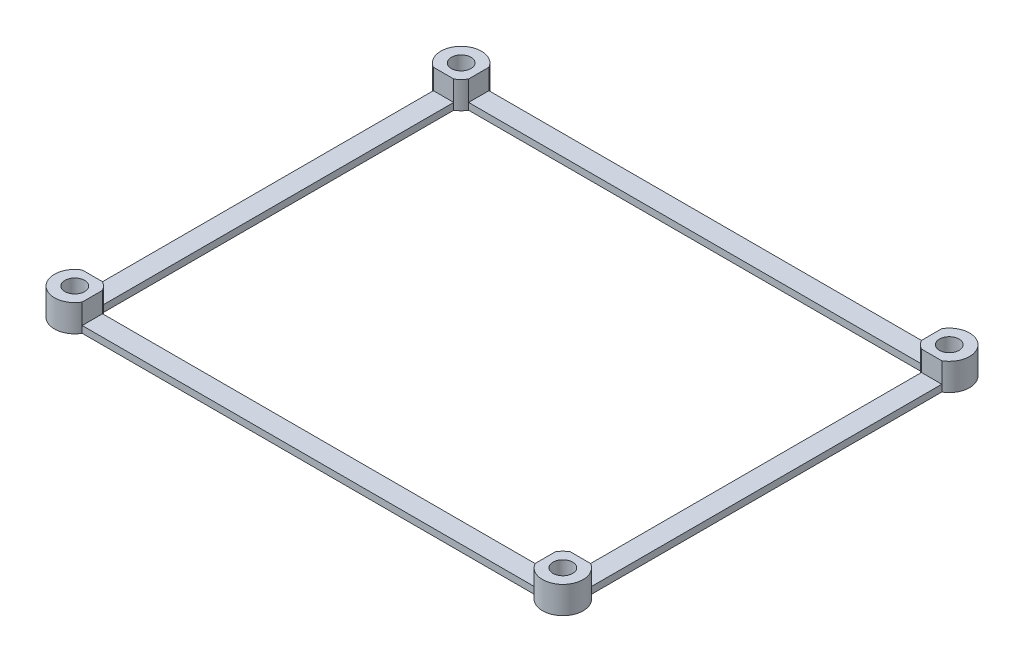
SolidWorks part; units mm, degrees
ref_plane "Front Plane" through (0, 0, 0) normal (0, 0, 1) x (1, 0, 0)
ref_plane "Top Plane" through (0, 0, 0) normal (0, 1, 0) x (1, 0, 0)
ref_plane "Right Plane" through (0, 0, 0) normal (1, 0, 0) x (0, 0, -1)
sketch "Sketch1" plane through (0, 0, 0) normal (0, 1, 0) x (1, 0, 0)
  line L1 (-36, -28.5) -> (36, -28.5) construction
  line L2 (-36, -28.5) -> (-36, 28.5) construction
  line L3 (-36, 28.5) -> (36, 28.5) construction
  line L4 (36, -28.5) -> (36, 28.5) construction
  line L5 (-36, -28.5) -> (36, 28.5) construction
  line L6 (-36, 28.5) -> (36, -28.5) construction
  line L7 (-33.4019, 27) -> (33.4019, 27)
  line L9 (-33.4019, 30) -> (33.4019, 30)
  line L11 (-33.4019, 27) -> (33.4019, 30) construction
  line L12 (-33.4019, 30) -> (33.4019, 27) construction
  line L14 (-37.5, -25.9019) -> (-37.5, 25.9019)
  line L16 (-34.5, -25.9019) -> (-34.5, 25.9019)
  line L17 (-37.5, -25.9019) -> (-34.5, 25.9019) construction
  line L18 (-37.5, 25.9019) -> (-34.5, -25.9019) construction
  line L20 (34.5, -25.9019) -> (34.5, 25.9019)
  line L22 (37.5, -25.9019) -> (37.5, 25.9019)
  line L23 (34.5, -25.9019) -> (37.5, 25.9019) construction
  line L24 (34.5, 25.9019) -> (37.5, -25.9019) construction
  line L25 (-33.4019, -30) -> (33.4019, -30)
  line L27 (-33.4019, -27) -> (33.4019, -27)
  line L29 (-33.4019, -30) -> (33.4019, -27) construction
  line L30 (-33.4019, -27) -> (33.4019, -30) construction
  circle A0 centre (36, 28.5) radius 1.45
  circle A1 centre (36, -28.5) radius 1.45
  circle A2 centre (-36, -28.5) radius 1.45
  circle A3 centre (-36, 28.5) radius 1.45
  arc A4 (-34.5, 25.9019) -> (-33.4019, 27) centre (-36, 28.5) ccw
  arc A5 (33.4019, 27) -> (34.5, 25.9019) centre (36, 28.5) ccw
  arc A6 (34.5, -25.9019) -> (33.4019, -27) centre (36, -28.5) ccw
  arc A7 (-33.4019, -27) -> (-34.5, -25.9019) centre (-36, -28.5) ccw
  arc A8 (-37.5, -25.9019) -> (-33.4019, -30) centre (-36, -28.5) ccw
  arc A9 (-33.4019, 30) -> (-37.5, 25.9019) centre (-36, 28.5) ccw
  arc A10 (37.5, 25.9019) -> (33.4019, 30) centre (36, 28.5) ccw
  arc A11 (33.4019, -30) -> (37.5, -25.9019) centre (36, -28.5) ccw
  point P0 (0, 0)
  point P14 (0, 28.5)
  point P19 (-36, 0)
  point P24 (36, 0)
  point P29 (0, -28.5)
  dimension "D3" = 2.9
  dimension "D4" = 6
  dimension "D1" = 72
  dimension "D2" = 57
  dimension "D5" = 3
  dimension "D6" = 3
  dimension "D7" = 3
  dimension "D8" = 3
extrude "Boss-Extrude1" add sketch "Sketch1" along normal blind 4
sketch "Sketch2" plane through (0, 4, 0) normal (0, 1, 0) x (1, 0, 0)
  line L1 (-37.5, 25.9019) -> (-34.5, 25.9019)
  line L2 (-37.5, 25.9019) -> (-37.5, -25.9019)
  line L3 (-37.5, -25.9019) -> (-34.5, -25.9019)
  line L4 (-34.5, 25.9019) -> (-34.5, -25.9019)
  line L5 (-33.4019, -27) -> (33.4019, -27)
  line L6 (-33.4019, -27) -> (-33.4019, -30)
  line L7 (-33.4019, -30) -> (33.4019, -30)
  line L8 (33.4019, -27) -> (33.4019, -30)
  line L9 (34.5, -25.9019) -> (37.5, -25.9019)
  line L10 (34.5, -25.9019) -> (34.5, 25.9019)
  line L11 (34.5, 25.9019) -> (37.5, 25.9019)
  line L12 (37.5, -25.9019) -> (37.5, 25.9019)
  line L13 (33.4019, 27) -> (-33.4019, 27)
  line L14 (33.4019, 27) -> (33.4019, 30)
  line L15 (33.4019, 30) -> (-33.4019, 30)
  line L16 (-33.4019, 27) -> (-33.4019, 30)
extrude "Cut-Extrude1" cut sketch "Sketch2" against normal offset from surface (3 mm away) 1 up to face at (-36, 0, -27.05)
